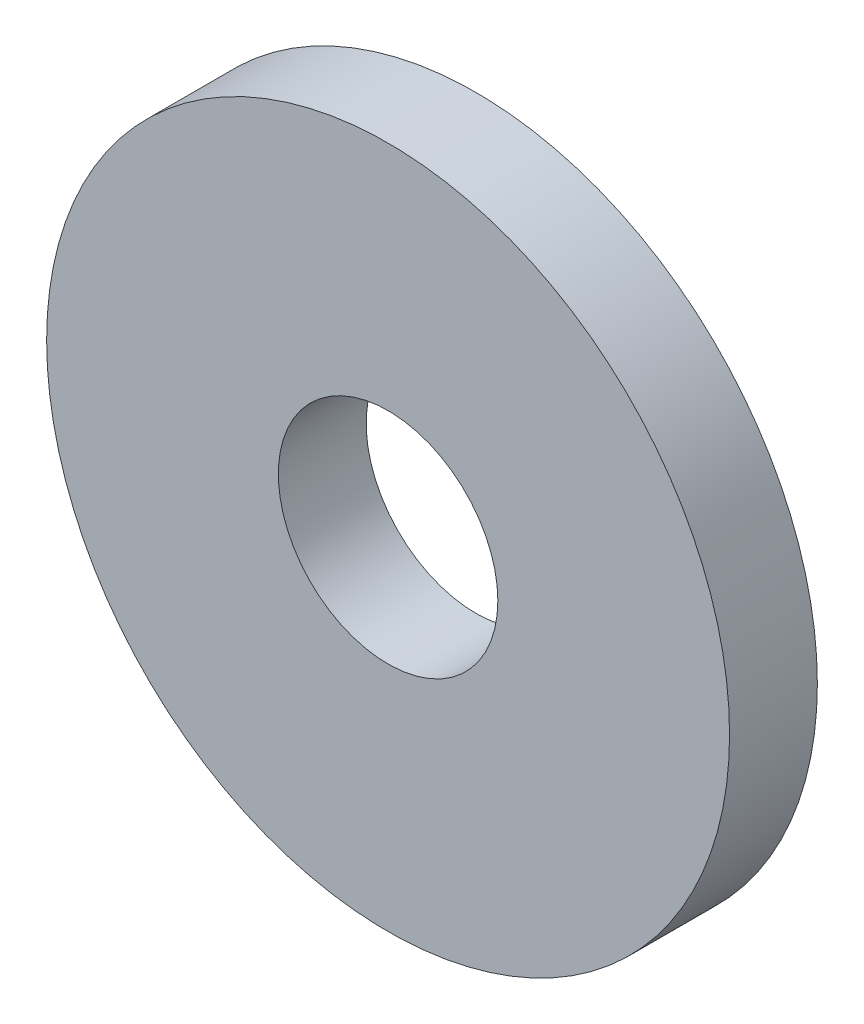
SolidWorks part; units mm, degrees
ref_plane "Front Plane" through (0, 0, 0) normal (0, 0, 1) x (1, 0, 0)
ref_plane "Top Plane" through (0, 0, 0) normal (0, 1, 0) x (1, 0, 0)
ref_plane "Right Plane" through (0, 0, 0) normal (1, 0, 0) x (0, 0, -1)
sketch "Sketch1" plane through (0, 0, 0) normal (0, 0, 1) x (1, 0, 0)
  circle A0 centre (0, 0) radius 14
  circle A1 centre (0, 0) radius 4.5
  dimension "OD" = 28
  dimension "ID1" = 9
extrude "Boss-Extrude1" add sketch "Sketch1" along normal blind 3.6
ref_axis "Center Axis 1" through (0, 0, 3.6) along (0, 0, -1)
ref_plane "Contact Plane 1" through (0, 0, 3.6) normal (0, 0, 1) x (1, 0, 0)
ref_plane "Contact Plane 2" through (0, 0, 0) normal (0, 0, -1) x (-1, 0, 0)
